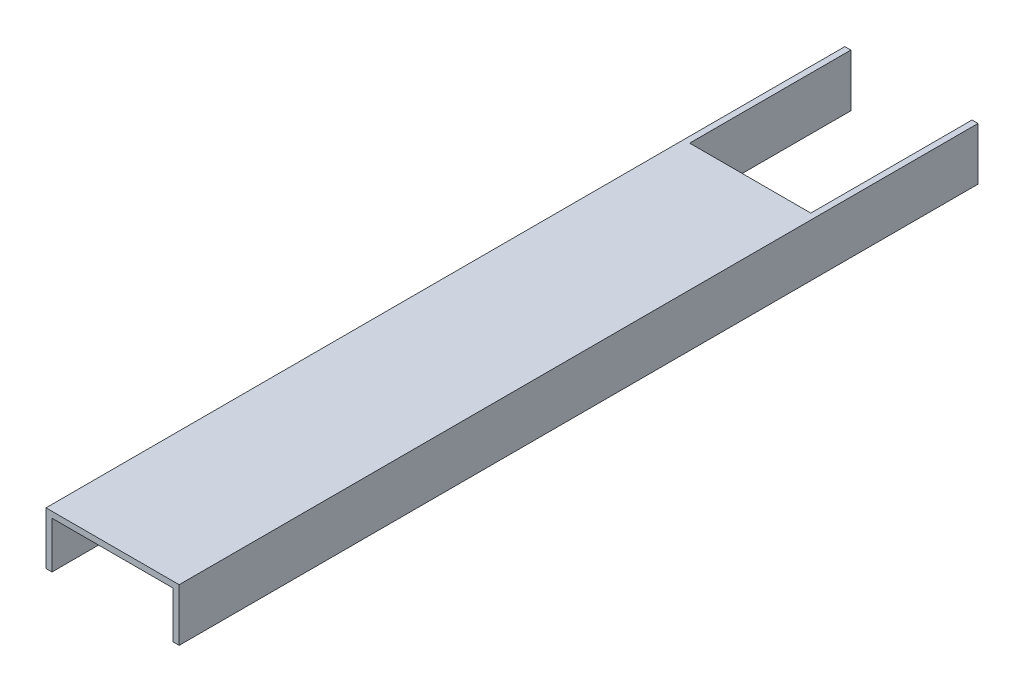
SolidWorks part; units mm, degrees
ref_plane "Front Plane" through (0, 0, 0) normal (0, 0, 1) x (1, 0, 0)
ref_plane "Top Plane" through (0, 0, 0) normal (0, 1, 0) x (1, 0, 0)
ref_plane "Right Plane" through (0, 0, 0) normal (1, 0, 0) x (0, 0, -1)
sketch "Sketch1" plane through (0, 0, 0) normal (0, 0, 1) x (1, 0, 0)
  line L0 (-50.8, 0) -> (50.8, 0)
  line L1 (50.8, 0) -> (50.8, -40.132)
  line L2 (50.8, -40.132) -> (46.228, -40.132)
  line L3 (46.228, -40.132) -> (46.228, -4.572)
  line L4 (46.228, -4.572) -> (-46.228, -4.572)
  line L5 (-46.228, -4.572) -> (-46.228, -40.132)
  line L6 (-46.228, -40.132) -> (-50.8, -40.132)
  line L7 (-50.8, -40.132) -> (-50.8, 0)
  point P8 (0, 0)
  dimension "D1" = 40.132
  dimension "D2" = 4.572
  dimension "D3" = 4.572
  dimension "D4" = 101.6
extrude "Boss-Extrude1" add sketch "Sketch1" along normal blind 609.6
sketch "Sketch3" plane through (0, 0, 0) normal (0, 1, 0) x (1, 0, 0)
  line L0 (50.8, 0) -> (-50.8, 0) construction
  line L1 (-46.228, -123.0155) -> (46.228, -123.0155)
  line L2 (-46.228, -123.0155) -> (-46.228, 0)
  line L3 (-46.228, 0) -> (46.228, 0)
  line L4 (46.228, -123.0155) -> (46.228, 0)
  line L5 (-46.228, -123.0155) -> (46.228, 0) construction
  line L6 (-46.228, 0) -> (46.228, -123.0155) construction
  line L7 (-46.228, -609.6) -> (-46.228, 0) construction
  line L8 (46.228, -609.6) -> (46.228, 0) construction
  point P0 (0, -61.5078)
  dimension "D1" = 123.0155
extrude "Cut-Extrude1" cut sketch "Sketch3" against normal through all
